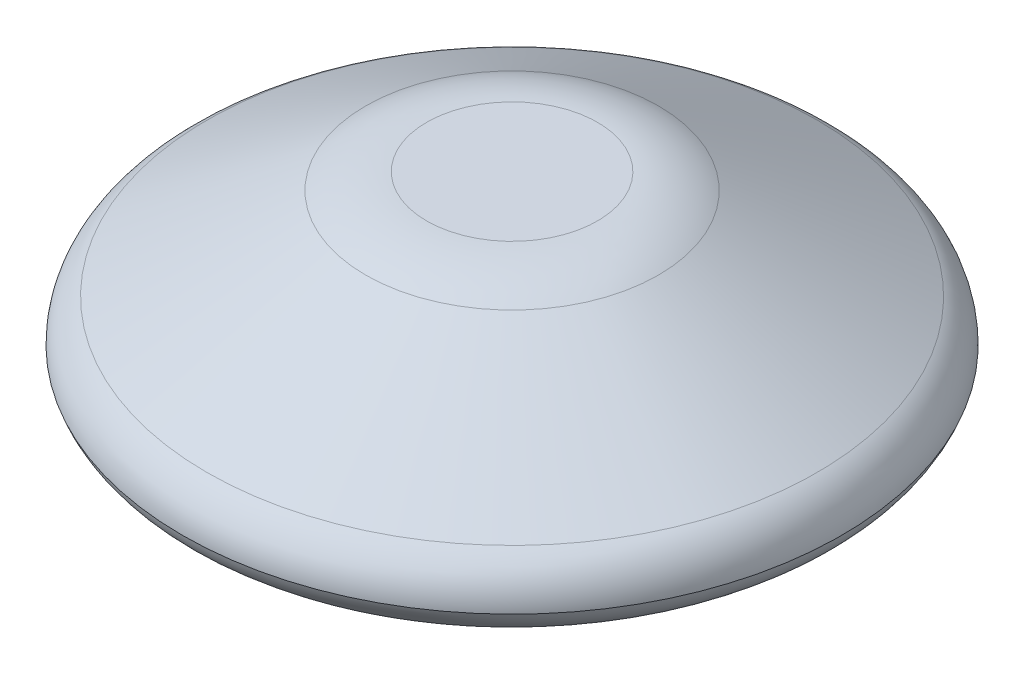
SolidWorks part; units mm, degrees
ref_plane "Ön Düzlem" through (0, 0, 0) normal (0, 0, 1) x (1, 0, 0)
ref_plane "Üst Düzlem" through (0, 0, 0) normal (0, 1, 0) x (1, 0, 0)
ref_plane "Sağ Düzlem" through (0, 0, 0) normal (1, 0, 0) x (0, 0, -1)
sketch "Çizim1" plane through (0, 0, 0) normal (0, 1, 0) x (1, 0, 0)
  circle A0 centre (0, 0) radius 27
  dimension "D1" = 54
extrude "Yükseklik-Ekstrüzyon1" add sketch "Çizim1" along normal blind 15
chamfer "Pah1" distance 10 angle 60 1 edges at (0, 15, 27) first distance on face at (0, 15, 27)
fillet "Radyus1" radius 10 1 edges at (0, 15, 9.6795)
fillet "Radyus2" radius 4 1 edges at (0, 5, 27)
fillet "Radyus3" radius 4 1 edges at (0, 0, 27)
sketch "Çizim2" plane through (0, 0, 0) normal (0, -1, 0) x (1, 0, 0)
  circle A0 centre (0, 0) radius 10
  dimension "D1" = 20
extrude "Kes-Ekstrüzyon1" cut sketch "Çizim2" against normal blind 2
